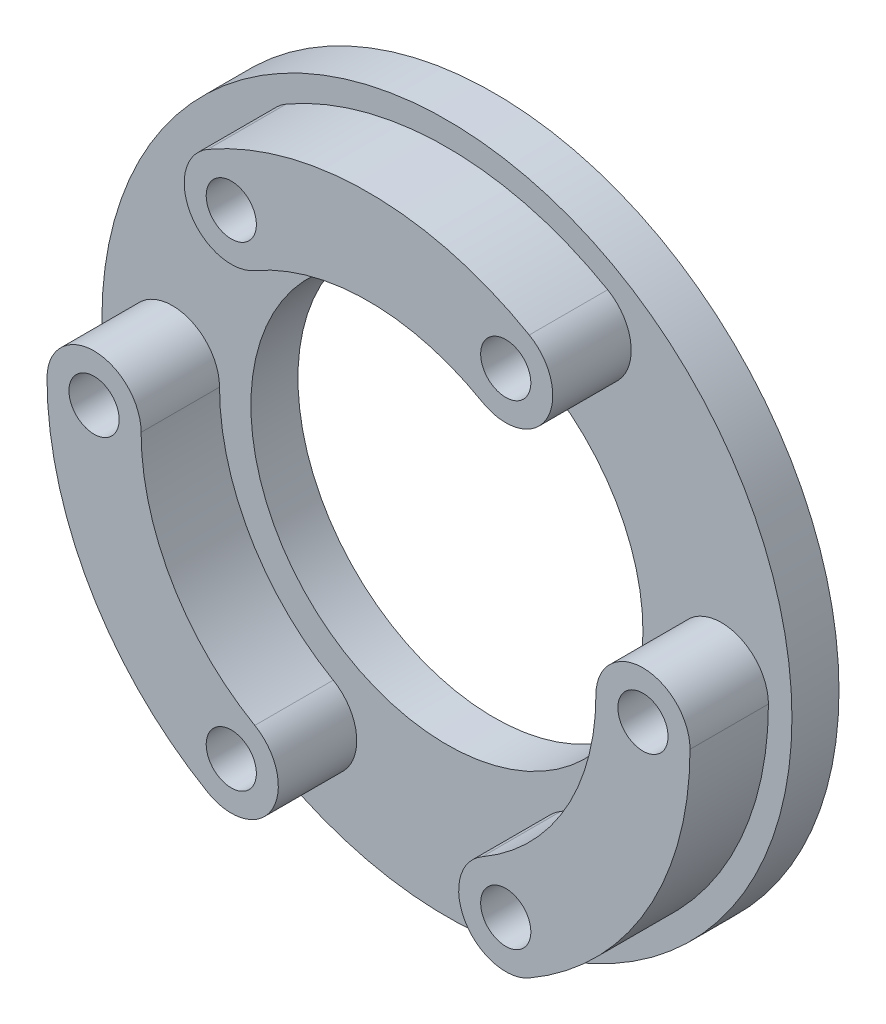
SolidWorks part; units mm, degrees
material "3.1325 (EN-AW 2017A)"
ref_plane "正面" through (0, 0, 0) normal (0, 0, 1) x (1, 0, 0)
ref_plane "平面" through (0, 0, 0) normal (0, 1, 0) x (1, 0, 0)
ref_plane "右側面" through (0, 0, 0) normal (1, 0, 0) x (0, 0, -1)
sketch "ｽｹｯﾁ1" plane through (0, 0, 0) normal (0, 0, 1) x (1, 0, 0)
  line L0 (0, 0) -> (0, 17.5) construction
  circle A0 centre (0, 0) radius 22
  circle A1 centre (0, 0) radius 12.5
  arc A2 (-8.75, 15.1554) -> (8.75, 15.1554) centre (0, 0) cw construction
  arc A3 (10.25, 17.7535) -> (-10.25, 17.7535) centre (0, 0) ccw
  arc A4 (7.25, 12.5574) -> (-7.25, 12.5574) centre (0, 0) ccw
  arc A5 (7.25, 12.5574) -> (10.25, 17.7535) centre (8.75, 15.1554) ccw
  arc A6 (-10.25, 17.7535) -> (-7.25, 12.5574) centre (-8.75, 15.1554) ccw
  arc A11 (17.5, 0) -> (8.75, -15.1554) centre (0, 0) cw construction
  arc A12 (10.25, -17.7535) -> (20.5, 0) centre (0, 0) ccw
  arc A13 (7.25, -12.5574) -> (14.5, 0) centre (0, 0) ccw
  arc A14 (7.25, -12.5574) -> (10.25, -17.7535) centre (8.75, -15.1554) ccw
  arc A15 (20.5, 0) -> (14.5, 0) centre (17.5, 0) ccw
  arc A18 (-8.75, -15.1554) -> (-17.5, 0) centre (0, 0) cw construction
  arc A19 (-20.5, 0) -> (-10.25, -17.7535) centre (0, 0) ccw
  arc A20 (-14.5, 0) -> (-7.25, -12.5574) centre (0, 0) ccw
  arc A21 (-14.5, 0) -> (-20.5, 0) centre (-17.5, 0) ccw
  arc A22 (-10.25, -17.7535) -> (-7.25, -12.5574) centre (-8.75, -15.1554) ccw
  point P6 (0, 17.5)
  point P22 (15.1554, -8.75)
  point P33 (-15.1554, -8.75)
  point P42 (0, 0)
  dimension "D1" = 25
  dimension "D2" = 44
  dimension "D3" = 6
  dimension "D5" = 35
  dimension "D4" = 60
  dimension "D7" = 3
extrude "ﾎﾞｽ - 押し出し1" add sketch "ｽｹｯﾁ1" along normal blind 3 contours A0 | A1
extrude "ﾎﾞｽ - 押し出し2" add sketch "ｽｹｯﾁ1<4>" along normal blind 8 contours A19 A22 A20 A21 | A3 A6 A4 A5 | A12 A15 A13 A14 region at (0, 16.393, 0) region at (14.1968, -8.1965, 0) region at (-14.1968, -8.1965, 0)
sketch "ｽｹｯﾁ1<4>" plane through (0, 0, 0) normal (0, 0, 1) x (1, 0, 0) same geometry as "ｽｹｯﾁ1"
hole_wizard "M3 すきま穴1" positions "3Dｽｹｯﾁ1" profile "ｽｹｯﾁ2" hole size "M3" standard "JIS" end condition through all
sketch3d "3Dｽｹｯﾁ1"
  point P0 (8.75, 15.1554, 0)
  point P2 (17.5, 0, 0)
  point P4 (8.75, -15.1554, 0)
  point P6 (-8.75, -15.1554, 0)
  point P8 (-17.5, 0, 0)
  point P10 (-8.75, 15.1554, 0)
sketch "ｽｹｯﾁ2" plane through (8.75, 15.1554, 0) normal (1, 0, 0) x (0, 1, 0)
  line L0 (0, 0) -> (0, 8)
  line L1 (0, 8) -> (1.6, 8)
  line L2 (1.6, 8) -> (1.6, 0)
  line L5 (1.6, 0) -> (0, 0)
  line L11 (0, -6.35) -> (0, 107.95) construction
  dimension "通し穴の直径" = 3.2
  dimension "通し穴の深さ" = 8
